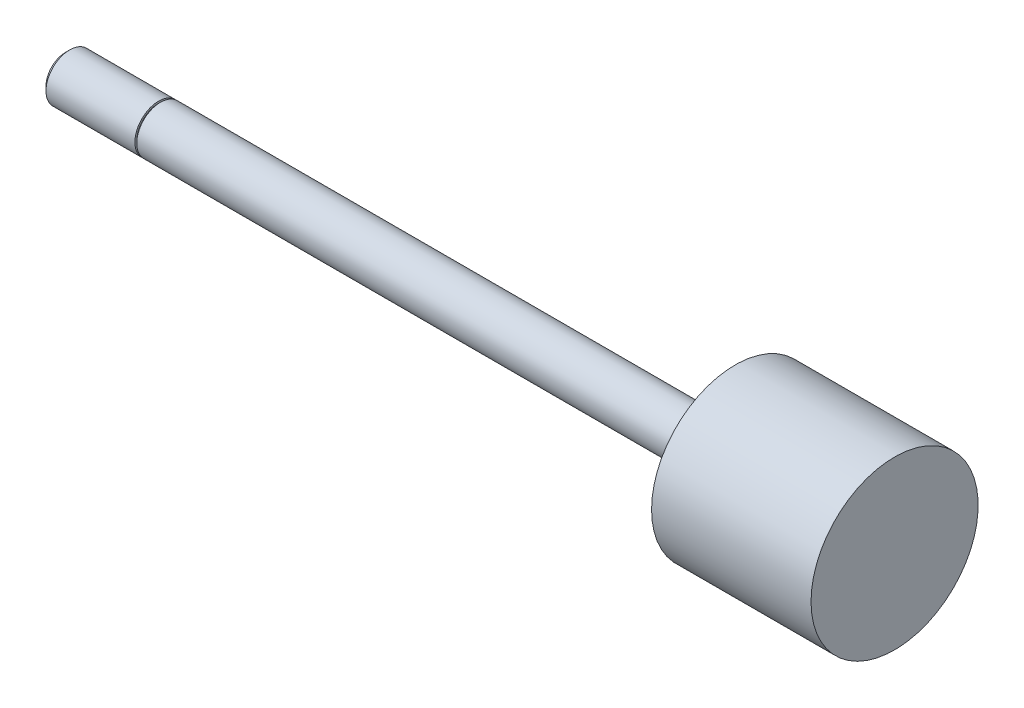
SolidWorks part; units mm, degrees
material "Plain Carbon Steel"
ref_plane "Front Plane" through (0, 0, 0) normal (0, 0, 1) x (1, 0, 0)
ref_plane "Top Plane" through (0, 0, 0) normal (0, 1, 0) x (1, 0, 0)
ref_plane "Right Plane" through (0, 0, 0) normal (1, 0, 0) x (0, 0, -1)
sketch "Sketch1" plane through (0, 0, 0) normal (0, 0, 1) x (1, 0, 0)
  line L0 (0, 0) -> (0, 3.175)
  line L1 (0, 3.175) -> (76.9874, 3.175)
  line L2 (76.9874, 3.175) -> (76.9874, 11.1951)
  line L3 (76.9874, 11.1951) -> (98.3488, 11.1951)
  line L4 (98.3488, 11.1951) -> (98.3488, 0)
  line L5 (98.3488, 0) -> (0, 0)
  line L6 (98.3488, 0) -> (0, 0) construction
revolve "Revolve1" add sketch "Sketch1" angle 360 about L6 reverse direction yes
sketch "Sketch2" plane through (0, 0, 0) normal (0, 0, 1) x (1, 0, 0)
  line L0 (-12.7, 0) -> (-12.7, 2.634)
  line L1 (-12.7, 2.634) -> (-12.159, 3.175)
  line L2 (-12.159, 3.175) -> (0, 3.175)
  line L3 (0, 3.175) -> (0, 0)
  line L4 (0, 0) -> (-12.7, 0)
  line L5 (0, 0) -> (-12.7, 0) construction
revolve "Revolve2" add sketch "Sketch2" angle 360 about L5 reverse direction yes
ref_plane "Plane1" through (0, 0, 0) normal (1, 0, 0) x (0, 0, -1)
ref_plane "Plane2" through (0, 0, 0) normal (1, 0, 0) x (0, 0, -1)
ref_plane "Plane3" through (175.3362, 0, 0) normal (1, 0, 0) x (0, 0, -1)
ref_plane "Plane4" through (-12.7, 0, 0) normal (1, 0, 0) x (0, 0, -1)
sketch "Sketch3" plane through (0, 0, 0) normal (0, 0, 1) x (1, 0, 0)
  line L0 (-0.254, 3.429) -> (-0.254, 2.921)
  line L1 (-0.254, 2.921) -> (0, 2.921)
  line L2 (0, 2.921) -> (0, 3.429)
  line L3 (0, 3.429) -> (-0.254, 3.429)
  line L4 (0, 0) -> (-0.254, 0) construction
revolve "Cut-Revolve1" cut sketch "Sketch3" angle 360 about L4 reverse direction yes
ref_plane "Plane5" through (0, 0, 0) normal (0, 0, 1) x (1, 0, 0)
ref_plane "Plane6" through (0, 0, 0) normal (1, 0, 0) x (0, 0, -1)
ref_plane "Plane7" through (-16.764, 0, 0) normal (1, 0, 0) x (0, 0, -1)
ref_plane "dia1 XY" through (0, 0, 0) normal (1, 0, 0) x (0, 0, -1)
ref_plane "dia1 XZ" through (0, 3.175, 0) normal (0, -1, 0) x (-1, 0, 0)
ref_plane "dia1 YZ" through (0, 0, 0) normal (0, 0, -1) x (-1, 0, 0)
ref_axis "dia1 X" through (0, 3.175, 80.9) along (0, 0, -1)
ref_axis "dia1 Y" through (0, -50, 0) along (0, 1, 0)
ref_axis "dia1 Z" through (80.9, 3.175, 0) along (-1, 0, 0)
sketch3d "dia1"
  point P0 (0, 3.175, 0)
ref_plane "dia12 XY" through (0, 0, 0) normal (1, 0, 0) x (0, 0, -1)
ref_plane "dia12 XZ" through (0, 0, 0) normal (0, -1, 0) x (-1, 0, 0)
ref_plane "dia12 YZ" through (0, 0, 11.7602) normal (0, 0, -1) x (-1, 0, 0)
ref_axis "dia12 X" through (0, 0, 80.9) along (0, 0, -1)
ref_axis "dia12 Y" through (0, -50, 11.7602) along (0, 1, 0)
ref_axis "dia12 Z" through (80.9, 0, 11.7602) along (-1, 0, 0)
sketch3d "dia12"
  point P0 (0, 0, 11.7602)
ref_plane "dia2 XY" through (0, 0, 0) normal (1, 0, 0) x (0, 0, -1)
ref_plane "dia2 XZ" through (0, -3.175, 0) normal (0, -1, 0) x (-1, 0, 0)
ref_plane "dia2 YZ" through (0, 0, 0) normal (0, 0, -1) x (-1, 0, 0)
ref_axis "dia2 X" through (0, -3.175, 80.9) along (0, 0, -1)
ref_axis "dia2 Y" through (0, -50, 0) along (0, 1, 0)
ref_axis "dia2 Z" through (80.9, -3.175, 0) along (-1, 0, 0)
sketch3d "dia2"
  point P0 (0, -3.175, 0)
ref_plane "dia22 XY" through (0, 0, 0) normal (1, 0, 0) x (0, 0, -1)
ref_plane "dia22 XZ" through (0, 0, 0) normal (0, -1, 0) x (-1, 0, 0)
ref_plane "dia22 YZ" through (0, 0, -11.7602) normal (0, 0, -1) x (-1, 0, 0)
ref_axis "dia22 X" through (0, 0, 80.9) along (0, 0, -1)
ref_axis "dia22 Y" through (0, -50, -11.7602) along (0, 1, 0)
ref_axis "dia22 Z" through (80.9, 0, -11.7602) along (-1, 0, 0)
sketch3d "dia22"
  point P0 (0, 0, -11.7602)
ref_plane "hh1 XY" through (0, 0, 0) normal (0, 0, 1) x (1, 0, 0)
ref_plane "hh1 XZ" through (0, 0, 0) normal (0, -1, 0) x (-1, 0, 0)
ref_plane "hh1 YZ" through (125.3236, 0, 0) normal (1, 0, 0) x (0, 0, -1)
ref_axis "hh1 X" through (-80.9, 0, 0) along (1, 0, 0)
ref_axis "hh1 Y" through (125.3236, -50, 0) along (0, 1, 0)
ref_axis "hh1 Z" through (125.3236, 0, 80.9) along (0, 0, -1)
sketch3d "hh1"
  point P0 (125.3236, 0, 0)
ref_plane "hh2 XY" through (0, 0, 0) normal (0, 0, 1) x (1, 0, 0)
ref_plane "hh2 XZ" through (0, 0, 0) normal (0, -1, 0) x (-1, 0, 0)
ref_plane "hh2 YZ" through (131.7244, 0, 0) normal (1, 0, 0) x (0, 0, -1)
ref_axis "hh2 X" through (-80.9, 0, 0) along (1, 0, 0)
ref_axis "hh2 Y" through (131.7244, -50, 0) along (0, 1, 0)
ref_axis "hh2 Z" through (131.7244, 0, 80.9) along (0, 0, -1)
sketch3d "hh2"
  point P0 (131.7244, 0, 0)
ref_plane "rl1 XY" through (-12.7, 0, 0) normal (1, 0, 0) x (0, 0, -1)
ref_plane "rl1 XZ" through (0, 0, 0) normal (0, -1, 0) x (-1, 0, 0)
ref_plane "rl1 YZ" through (0, 0, 0) normal (0, 0, -1) x (-1, 0, 0)
ref_axis "rl1 X" through (-12.7, 0, 80.9) along (0, 0, -1)
ref_axis "rl1 Y" through (-12.7, -50, 0) along (0, 1, 0)
ref_axis "rl1 Z" through (80.9, 0, 0) along (-1, 0, 0)
sketch3d "rl1"
  point P0 (-12.7, 0, 0)
ref_plane "rl2 XY" through (0, 0, 0) normal (1, 0, 0) x (0, 0, -1)
ref_plane "rl2 XZ" through (0, 0, 0) normal (0, -1, 0) x (-1, 0, 0)
ref_plane "rl2 YZ" through (0, 0, 0) normal (0, 0, -1) x (-1, 0, 0)
ref_axis "rl2 X" through (0, 0, 80.9) along (0, 0, -1)
ref_axis "rl2 Y" through (0, -50, 0) along (0, 1, 0)
ref_axis "rl2 Z" through (80.9, 0, 0) along (-1, 0, 0)
sketch3d "rl2"
  point P0 (0, 0, 0)
ref_plane "rod_cp XY" through (0, 0, 0) normal (1, 0, 0) x (0, 0, -1)
ref_plane "rod_cp XZ" through (0, 0, 0) normal (0, -1, 0) x (-1, 0, 0)
ref_plane "rod_cp YZ" through (0, 0, 0) normal (0, 0, -1) x (-1, 0, 0)
ref_axis "rod_cp X" through (0, 0, 80.9) along (0, 0, -1)
ref_axis "rod_cp Y" through (0, -50, 0) along (0, 1, 0)
ref_axis "rod_cp Z" through (80.9, 0, 0) along (-1, 0, 0)
sketch3d "rod_cp"
  point P0 (0, 0, 0)
ref_plane "thd1 XY" through (-12.7, 0, 0) normal (1, 0, 0) x (0, 0, -1)
ref_plane "thd1 XZ" through (0, 3.175, 0) normal (0, -1, 0) x (-1, 0, 0)
ref_plane "thd1 YZ" through (0, 0, 0) normal (0, 0, -1) x (-1, 0, 0)
ref_axis "thd1 X" through (-12.7, 3.175, 80.9) along (0, 0, -1)
ref_axis "thd1 Y" through (-12.7, -50, 0) along (0, 1, 0)
ref_axis "thd1 Z" through (80.9, 3.175, 0) along (-1, 0, 0)
sketch3d "thd1"
  point P0 (-12.7, 3.175, 0)
ref_plane "thd2 XY" through (-12.7, 0, 0) normal (1, 0, 0) x (0, 0, -1)
ref_plane "thd2 XZ" through (0, -3.175, 0) normal (0, -1, 0) x (-1, 0, 0)
ref_plane "thd2 YZ" through (0, 0, 0) normal (0, 0, -1) x (-1, 0, 0)
ref_axis "thd2 X" through (-12.7, -3.175, 80.9) along (0, 0, -1)
ref_axis "thd2 Y" through (-12.7, -50, 0) along (0, 1, 0)
ref_axis "thd2 Z" through (80.9, -3.175, 0) along (-1, 0, 0)
sketch3d "thd2"
  point P0 (-12.7, -3.175, 0)
ref_plane "to_rod_clevis XY" through (-16.764, 0, 0) normal (1, 0, 0) x (0, 0, -1)
ref_plane "to_rod_clevis XZ" through (0, 0, 0) normal (0, -1, 0) x (-1, 0, 0)
ref_plane "to_rod_clevis YZ" through (0, 0, 0) normal (0, 0, -1) x (-1, 0, 0)
ref_axis "to_rod_clevis X" through (-16.764, 0, 80.9) along (0, 0, -1)
ref_axis "to_rod_clevis Y" through (-16.764, -50, 0) along (0, 1, 0)
ref_axis "to_rod_clevis Z" through (80.9, 0, 0) along (-1, 0, 0)
sketch3d "to_rod_clevis"
  point P0 (-16.764, 0, 0)
